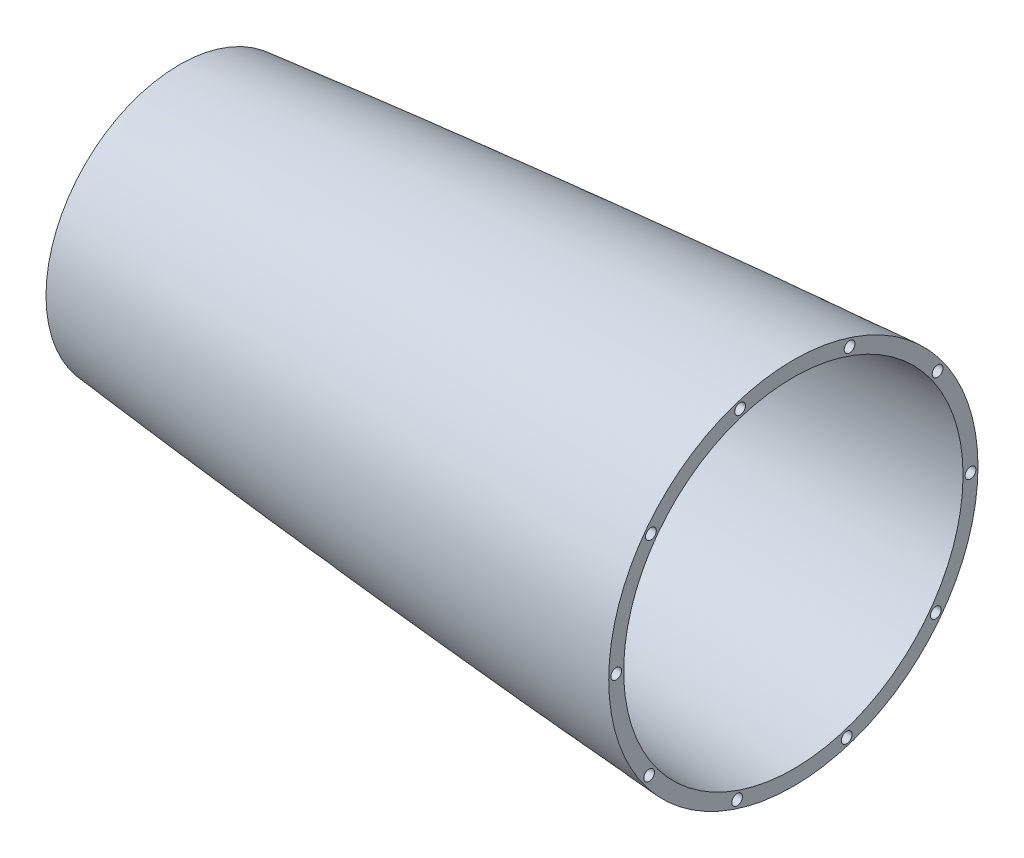
SolidWorks part; units mm, degrees
ref_plane "Front Plane" through (0, 0, 0) normal (0, 0, 1) x (1, 0, 0)
ref_plane "Top Plane" through (0, 0, 0) normal (0, 1, 0) x (1, 0, 0)
ref_plane "Right Plane" through (0, 0, 0) normal (1, 0, 0) x (0, 0, -1)
sketch "Sketch1" plane through (0, 0, 0) normal (0, 0, 1) x (1, 0, 0)
  line L2 (0, -76.2) -> (-921.7152, -76.2) construction
  line L3 (6.35, 6.35) -> (6.35, 0)
  line L4 (-259.8125, 11.4606) -> (6.35, 11.4606)
  line L5 (0, 0) -> (6.35, 0)
  line L6 (6.35, 6.35) -> (6.35, -76.2) construction
  line L7 (0, 0) -> (0, -76.2) construction
  line L8 (-921.7152, -58.5997) -> (-928.0652, -58.5997)
  line L9 (-928.0652, -58.5997) -> (-928.0652, -76.2) construction
  line L10 (-921.7152, -58.5997) -> (-921.7152, -76.2) construction
  line L11 (6.35, 11.4606) -> (6.35, 6.35)
  arc A0 (-254, 2.1118) -> (-248.4137, -0.891) centre (-248.6021, 5.4563) ccw
  arc A2 (-916.3053, -52.3197) -> (-921.7152, -58.5997) centre (-915.3652, -58.5997) ccw
  arc A4 (-254, 2.1118) -> (-259.6052, 5.114) centre (-259.3979, -1.2327) ccw
  arc A6 (-248.6021, 5.4563) -> (-248.6021, 5.4563) centre (-248.6021, 5.4563) ccw
  arc A7 (-248.6021, 5.4563) -> (-259.8125, 11.4606) centre (-259.3979, -1.2327) ccw
  arc A8 (-917.2454, -46.0396) -> (-928.0652, -58.5997) centre (-915.3652, -58.5997) ccw
  spline S0 degree 3 poles (0, 0) (-50.8, 0) (-101.6, 0) (-157.1824, 0) (-166.7471, 0) (-181.0943, 0) (-190.659, 0) (-199.5851, 0) (-207.8726, 0) (-220.3048, -0.155) (-228.5897, -0.3615) (-235.0947, -0.5237) (-239.8196, -0.6415) (-245.0466, -0.7915) (-247.9113, -0.876) (-248.4137, -0.891) knots 0.761574 0.761574 0.761574 0.761574 0.907842 0.907842 0.921611 0.935381 0.949151 0.949151 0.961082 0.973013 0.984944 0.984944 0.991748 0.998553 1 1 1 1
  spline S1 degree 1 poles (6.35, 6.35) (-248.6021, 5.4563) knots 0 0 1 1 construction
  spline S2 degree 3 poles (-259.6052, 5.114) (-267.1277, 4.8682) (-283.426, 4.2857) (-317.2703, 2.8805) (-361.13, 0.7112) (-431.2755, -3.372) (-501.3729, -8.2669) (-571.4145, -13.8917) (-623.9147, -18.4777) (-676.3803, -23.4393) (-728.8057, -28.7991) (-772.4536, -33.6275) (-807.3418, -37.7392) (-833.4907, -40.9589) (-859.6194, -44.3289) (-885.7239, -47.8693) (-904.6125, -50.5779) (-914.801, -52.0945) (-916.3053, -52.3197) knots 0.121539 0.121539 0.121539 0.121539 0.143123 0.168303 0.218664 0.269025 0.369746 0.420107 0.470467 0.520828 0.571189 0.62155 0.64673 0.67191 0.697091 0.722271 0.747451 0.751814 0.751814 0.751814 0.751814
  spline S3 degree 1 poles (-259.8125, 11.4606) (-917.2454, -46.0396) knots 0 0 1 1 construction
  spline S4 degree 3 poles (6.35, 6.35) (-14.881, 6.35) (-57.3424, 6.3506) (-110.4226, 6.3484) (-152.8795, 6.3528) (-179.4314, 6.3414) (-200.6356, 6.3648) (-216.6826, 6.282) (-232.6614, 5.8947) (-243.2867, 5.614) (-248.6021, 5.4563) knots 0.75548 0.75548 0.75548 0.75548 0.81661 0.87774 0.908305 0.93887 0.954152 0.969435 0.984717 1 1 1 1
  spline S5 degree 3 poles (-259.8125, 11.4606) (-287.3121, 10.5623) (-342.298, 8.1716) (-452.1401, 1.8335) (-589.2803, -8.5121) (-726.1766, -21.7709) (-835.4658, -34.5887) (-890.027, -41.9652) (-917.2454, -46.0396) knots 0.121539 0.121539 0.121539 0.121539 0.200324 0.279108 0.436676 0.594245 0.673029 0.751814 0.751814 0.751814 0.751814
revolve "Revolve1" add sketch "Sketch1" angle 360 about L2 region at (-124.3289, 8.8839, 0) region at (-3.0204, 3.175, 0)
ref_plane "Plane1" through (-438.15, 0, 0) normal (1, 0, 0) x (0, 0, -1)
sketch "Sketch8" plane through (-438.15, 0, 0) normal (1, 0, 0) x (0, 0, -1)
  circle A0 centre (0, -76.2) radius 87.6606 construction
  circle A1 centre (0, -76.2) radius 87.6606 construction
  circle A2 centre (0, -76.2) radius 142.3459
extrude "Cut-Extrude4" cut sketch "Sketch8" along normal through all
sketch "Sketch9" plane through (-438.15, 0, 0) normal (1, 0, 0) x (0, 0, -1)
  line L0 (0, 0) -> (0, -76.2) construction
  line L1 (0, -76.2) -> (23.926, -4.6927) construction
  circle A0 centre (0, -76.2) radius 72.2219 construction
  circle A1 centre (0, -76.2) radius 78.586 construction
  circle A2 centre (0, -76.2) radius 72.2219 construction
  circle A3 centre (0, -76.2) radius 78.586 construction
  circle A4 centre (0, -76.2) radius 75.4039 construction
  circle A5 centre (23.926, -4.6927) radius 2.286
  circle A6 centre (61.3875, -32.4127) radius 2.286
  circle A7 centre (75.4011, -76.858) radius 2.286
  circle A8 centre (60.614, -121.052) radius 2.286
  circle A9 centre (22.6744, -148.114) radius 2.286
  circle A10 centre (-23.926, -147.7073) radius 2.286
  circle A11 centre (-61.3875, -119.9873) radius 2.286
  circle A12 centre (-75.4011, -75.542) radius 2.286
  circle A13 centre (-60.614, -31.348) radius 2.286
  circle A14 centre (-22.6744, -4.286) radius 2.286
  point P31 (0, -76.2)
  dimension "D1" = 6.364
  dimension "D2" = 3.182
  dimension "D3" = 4.572
  dimension "D4" = 18.5
  dimension "D5" = 10
extrude "Cut-Extrude5" cut sketch "Sketch9" against normal blind 10.16
ref_plane "Plane3" through (-928.0652, 0, 0) normal (1, 0, 0) x (0, 0, -1)
sketch "Sketch10" plane through (-928.0652, 0, 0) normal (1, 0, 0) x (0, 0, -1)
  circle A0 centre (0, -76.2) radius 78.586 construction
  circle A1 centre (0, -76.2) radius 78.586 construction
  circle A2 centre (0, -76.2) radius 97.8804
extrude "Cut-Extrude6" cut sketch "Sketch10" along normal blind 228.6
